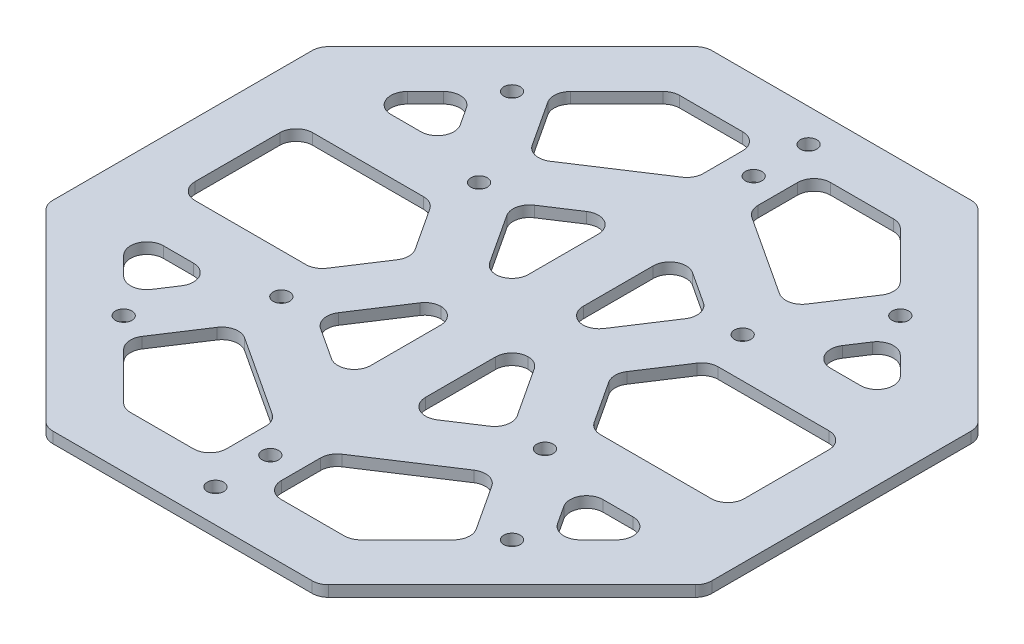
SolidWorks part; units mm, degrees
ref_plane "前视基准面" through (0, 0, 0) normal (0, 0, 1) x (1, 0, 0)
ref_plane "上视基准面" through (0, 0, 0) normal (0, 1, 0) x (1, 0, 0)
ref_plane "右视基准面" through (0, 0, 0) normal (1, 0, 0) x (0, 0, -1)
other "Configuration Table"
sketch "草图1" plane through (0, 0, 0) normal (0, 1, 0) x (1, 0, 0)
  line L0 (-24.8528, 60) -> (24.8528, 60)
  line L1 (24.8528, 60) -> (60, 24.8528)
  line L2 (60, 24.8528) -> (60, -24.8528)
  line L3 (60, -24.8528) -> (24.8528, -60)
  line L4 (24.8528, -60) -> (-24.8528, -60)
  line L5 (-24.8528, -60) -> (-60, -24.8528)
  line L6 (-60, -24.8528) -> (-60, 24.8528)
  line L7 (-60, 24.8528) -> (-24.8528, 60)
  line L8 (0, 0) -> (60, 0) construction
  line L9 (0, 0) -> (0, 60) construction
  line L10 (0, 0) -> (35.3553, 35.3553) construction
  circle A0 centre (-24, 18) radius 1.5
  circle A2 centre (24, 18) radius 1.5
  circle A3 centre (24, -18) radius 1.5
  circle A4 centre (-24, -18) radius 1.5
  circle A5 centre (35.3553, 35.3553) radius 1.5
  circle A6 centre (0, 0) radius 50 construction
  circle A7 centre (35.3553, -35.3553) radius 1.5
  circle A8 centre (-35.3553, -35.3553) radius 1.5
  circle A9 centre (-35.3553, 35.3553) radius 1.5
  circle A10 centre (0, 54) radius 1.5
  circle A11 centre (0, 44) radius 1.5
  circle A12 centre (0, -44) radius 1.5
  circle A13 centre (0, -54) radius 1.5
  point P31 (0, 0)
  dimension "D3" = 3
  dimension "D6" = 100
  dimension "D7" = 3
  dimension "D12" = 3
  dimension "D1" = 135
  dimension "D2" = 120
  dimension "D4" = 36
  dimension "D5" = 48
  dimension "D9" = 45
  dimension "D10" = 10
  dimension "D11" = 6
  dimension "D8" = 4
extrude "凸台-拉伸1" add sketch "草图1" along normal blind 2 contours L7 L6 L5 L4 L3 L2 L1 L0 A9 A8 A7 A5 A2 A0 A3 A4 | L6 | L2 region at (0, 0, 0)
fillet "圆角1" radius 3 8 edges at (-24.8528, 1, -60) (24.8528, 1, -60) (60, 1, -24.8528) (60, 1, 24.8528) (24.8528, 1, 60) (-60, 1, 24.8528) (-60, 1, -24.8528) (-24.8528, 1, 60)
sketch "草图2" plane through (0, 0, 0) normal (0, -1, 0) x (1, 0, 0)
  line L0 (-50, 20.7107) -> (-38.9673, 31.7434)
  line L1 (-38.9673, 31.7434) -> (-31.7487, 20.7107)
  line L2 (-31.7487, 20.7107) -> (-50, 20.7107)
  line L3 (-50, 10.7107) -> (-25.2058, 10.7107)
  line L4 (-25.2058, 10.7107) -> (-18.198, 0)
  line L8 (-50, 10.7107) -> (-50, -10.7107)
  line L12 (-20.7107, 50) -> (-31.7434, 38.9673)
  line L14 (-23.3807, 26.1857) -> (-5, 38.2119)
  line L15 (-5, 38.2119) -> (-5, 50)
  line L16 (-5, 50) -> (-20.7107, 50)
  line L17 (-60, 23.6102) -> (-60, -23.6102) construction
  line L18 (-25.7315, 59.1213) -> (-59.1213, 25.7315) construction
  line L19 (23.6102, 60) -> (-23.6102, 60) construction
  line L20 (0, 0) -> (0, 60) construction
  line L21 (-31.7434, 38.9673) -> (-23.3807, 26.1857)
  line L22 (-35.3553, 35.3553) -> (-24, 18) construction
  line L23 (0, 0) -> (-18.198, 0) construction
  line L24 (-18.198, 0) -> (-50, 0) construction
  line L25 (-17.9056, 17.8177) -> (-9.5192, 5)
  line L26 (-9.5192, 5) -> (-5, 5)
  line L27 (-5, 5) -> (-5, 26.2617)
  line L28 (-5, 26.2617) -> (-17.9056, 17.8177)
  line L29 (-31.7487, 20.7107) -> (-23.3807, 26.1857) construction
  line L30 (-25.2058, -10.7107) -> (-18.198, 0)
  line L31 (-31.7487, -20.7107) -> (-23.3807, -26.1857) construction
  line L32 (-35.3553, -35.3553) -> (-24, -18) construction
  line L33 (-5, -26.2617) -> (-17.9056, -17.8177)
  line L34 (-5, -5) -> (-5, -26.2617)
  line L35 (-9.5192, -5) -> (-5, -5)
  line L36 (-17.9056, -17.8177) -> (-9.5192, -5)
  line L37 (-31.7434, -38.9673) -> (-23.3807, -26.1857)
  line L38 (-5, -50) -> (-20.7107, -50)
  line L39 (-5, -38.2119) -> (-5, -50)
  line L40 (-23.3807, -26.1857) -> (-5, -38.2119)
  line L41 (-20.7107, -50) -> (-31.7434, -38.9673)
  line L42 (-50, -10.7107) -> (-25.2058, -10.7107)
  line L43 (-31.7487, -20.7107) -> (-50, -20.7107)
  line L44 (-38.9673, -31.7434) -> (-31.7487, -20.7107)
  line L45 (-50, -20.7107) -> (-38.9673, -31.7434)
  line L46 (35.3553, -35.3553) -> (24, -18) construction
  line L47 (31.7487, -20.7107) -> (23.3807, -26.1857) construction
  line L48 (31.7487, 20.7107) -> (23.3807, 26.1857) construction
  line L49 (18.198, 0) -> (50, 0) construction
  line L50 (35.3553, 35.3553) -> (24, 18) construction
  line L51 (50, -20.7107) -> (38.9673, -31.7434)
  line L52 (38.9673, -31.7434) -> (31.7487, -20.7107)
  line L53 (31.7487, -20.7107) -> (50, -20.7107)
  line L54 (50, -10.7107) -> (25.2058, -10.7107)
  line L55 (20.7107, -50) -> (31.7434, -38.9673)
  line L56 (23.3807, -26.1857) -> (5, -38.2119)
  line L57 (5, -38.2119) -> (5, -50)
  line L58 (5, -50) -> (20.7107, -50)
  line L59 (31.7434, -38.9673) -> (23.3807, -26.1857)
  line L60 (17.9056, -17.8177) -> (9.5192, -5)
  line L61 (9.5192, -5) -> (5, -5)
  line L62 (5, -5) -> (5, -26.2617)
  line L63 (5, -26.2617) -> (17.9056, -17.8177)
  line L64 (25.2058, -10.7107) -> (18.198, 0)
  line L65 (5, 26.2617) -> (17.9056, 17.8177)
  line L66 (5, 5) -> (5, 26.2617)
  line L67 (9.5192, 5) -> (5, 5)
  line L68 (17.9056, 17.8177) -> (9.5192, 5)
  line L69 (31.7434, 38.9673) -> (23.3807, 26.1857)
  line L70 (5, 50) -> (20.7107, 50)
  line L71 (5, 38.2119) -> (5, 50)
  line L72 (23.3807, 26.1857) -> (5, 38.2119)
  line L73 (20.7107, 50) -> (31.7434, 38.9673)
  line L74 (50, 10.7107) -> (50, -10.7107)
  line L75 (25.2058, 10.7107) -> (18.198, 0)
  line L76 (50, 10.7107) -> (25.2058, 10.7107)
  line L77 (31.7487, 20.7107) -> (50, 20.7107)
  line L78 (38.9673, 31.7434) -> (31.7487, 20.7107)
  line L79 (50, 20.7107) -> (38.9673, 31.7434)
  dimension "D1" = 10
  dimension "D2" = 10
  dimension "D3" = 5
  dimension "D4" = 10
  dimension "D5" = 5
  dimension "D6" = 10
  dimension "D7" = 10
  dimension "D8" = 10
  dimension "D9" = 5
extrude "切除-拉伸1" cut sketch "草图2" against normal blind 10
fillet "圆角2" radius 3 58 edges at (-50, 1, 20.7107) (-38.9673, 1, 31.7434) (-31.7487, 1, 20.7107) (5, 1, 38.2119) (5, 1, 50) (31.7434, 1, 38.9673) (23.3807, 1, 26.1857) (38.9673, 1, 31.7434) (50, 1, 20.7107) (31.7487, 1, 20.7107) (25.2058, 1, 10.7107) (50, 1, 10.7107) (50, 1, -10.7107) (25.2058, 1, -10.7107) (18.198, 1, 0) (5, 1, -26.2617) (5, 1, -5) (9.5192, 1, -5) (17.9056, 1, -17.8177) (5, 1, 26.2617) (17.9056, 1, 17.8177) (9.5192, 1, 5) (5, 1, 5) (-38.9673, 1, -31.7434) (-50, 1, -20.7107) (-31.7487, 1, -20.7107) (-5, 1, 50) (-5, 1, 38.2119) (-23.3807, 1, 26.1857) (-31.7434, 1, 38.9673) (-20.7107, 1, 50) (-5, 1, 26.2617) (-5, 1, 5) (-9.5192, 1, 5) (-17.9056, 1, 17.8177) (-50, 1, 10.7107) (-25.2058, 1, 10.7107) (-18.198, 1, 0) (-25.2058, 1, -10.7107) (-50, 1, -10.7107) (-5, 1, -26.2617) (-17.9056, 1, -17.8177) (-9.5192, 1, -5) (-5, 1, -5) (-5, 1, -38.2119) (-5, 1, -50) (-20.7107, 1, -50) (-31.7434, 1, -38.9673) (-23.3807, 1, -26.1857) (31.7434, 1, -38.9673) (20.7107, 1, -50) (5, 1, -50) (5, 1, -38.2119) (23.3807, 1, -26.1857) (50, 1, -20.7107) (38.9673, 1, -31.7434) (31.7487, 1, -20.7107) (20.7107, 1, 50)
